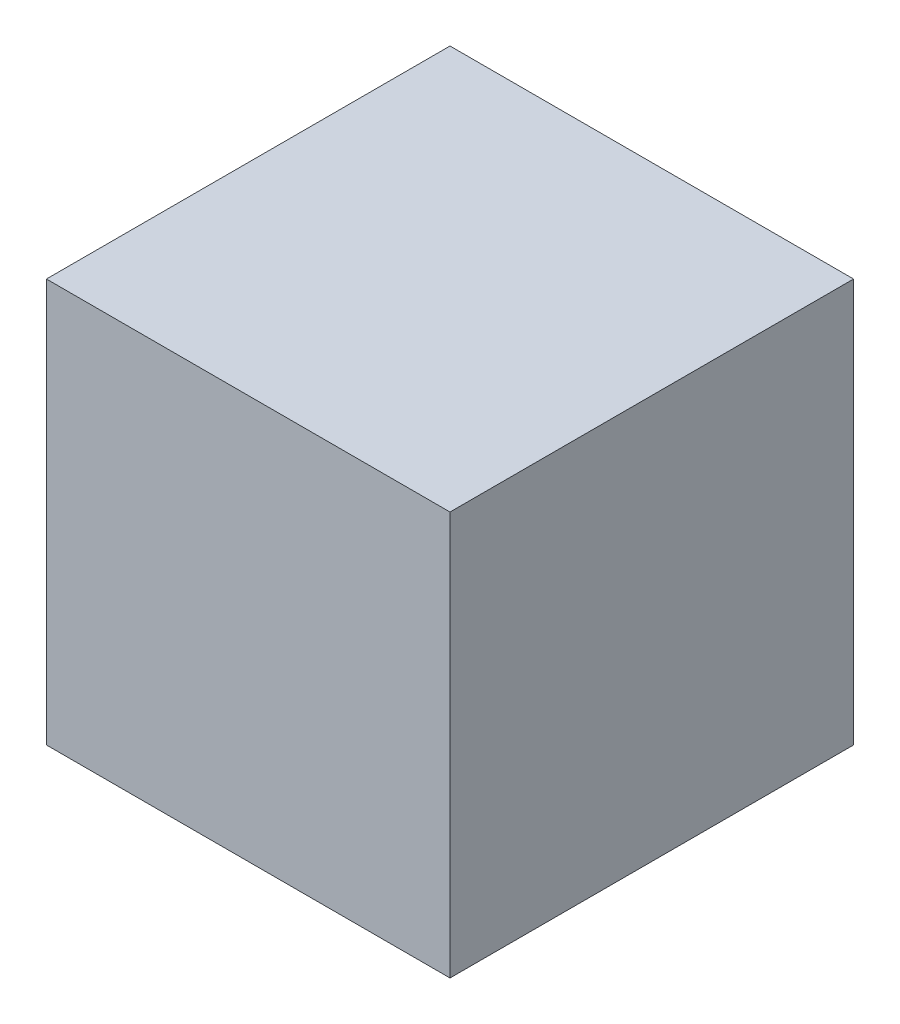
SolidWorks part; units mm, degrees
ref_plane "Front Plane" through (0, 0, 0) normal (0, 0, 1) x (1, 0, 0)
ref_plane "Top Plane" through (0, 0, 0) normal (0, 1, 0) x (1, 0, 0)
ref_plane "Right Plane" through (0, 0, 0) normal (1, 0, 0) x (0, 0, -1)
sketch "Sketch1" plane through (0, 0, 0) normal (0, 0, 1) x (1, 0, 0)
  line L6 (-4.1, -3.8617) -> (32.9, -3.8617)
  line L7 (-4.1, -3.8617) -> (-4.1, 33.1383)
  line L8 (-4.1, 33.1383) -> (32.9, 33.1383)
  line L9 (32.9, -3.8617) -> (32.9, 33.1383)
extrude "Boss-Extrude1" add sketch "Sketch1" along normal blind 37
